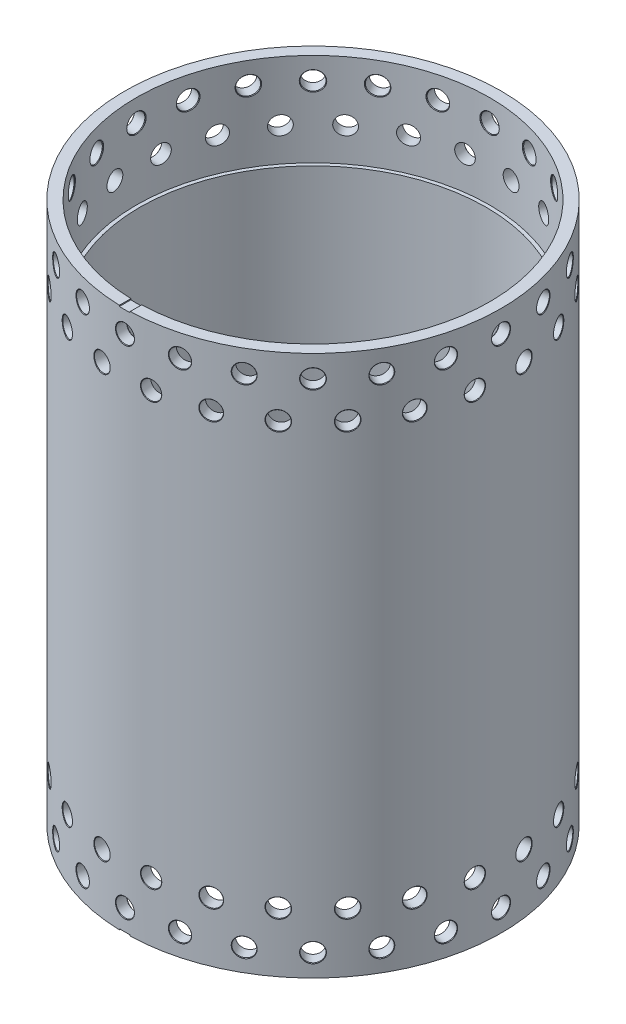
SolidWorks part; units mm, degrees
material "AW-6082-T6 (PA4)"
ref_plane "Płaszczyzna przednia" through (0, 0, 0) normal (0, 0, 1) x (1, 0, 0)
ref_plane "Płaszczyzna górna" through (0, 0, 0) normal (0, 1, 0) x (1, 0, 0)
ref_plane "Płaszczyzna prawa" through (0, 0, 0) normal (1, 0, 0) x (0, 0, -1)
sketch "Szkic1" plane through (0, 0, 0) normal (0, 1, 0) x (1, 0, 0)
  circle A0 centre (0, 0) radius 90
  circle A1 centre (0, 0) radius 80
  dimension "D1" = 10
  dimension "D2" = 180
  dimension "D3" = 160
extrude "Dodanie-wyciągnięcie1" add sketch "Szkic1" along normal blind 250
sketch "Szkic2" plane through (0, 250, 0) normal (0, 1, 0) x (1, 0, 0)
  circle A0 centre (0, 0) radius 87
  circle A1 centre (0, 0) radius 90 construction
  circle A2 centre (0, 0) radius 90
  dimension "D1" = 174
extrude "Wytnij-wyciągnięcie1" cut sketch "Szkic2" against normal through all
sketch "Szkic3" plane through (0, 250, 0) normal (0, 1, 0) x (1, 0, 0)
  circle A0 centre (0, 0) radius 81.7
  circle A1 centre (0, 0) radius 80 construction
  circle A2 centre (0, 0) radius 80
  dimension "D1" = 163.4
extrude "Wytnij-wyciągnięcie2" cut sketch "Szkic3" against normal blind 43
ref_plane "Płaszczyzna1" through (0, 0, 87) normal (0, 0, 1) x (1, 0, 0)
ref_plane "Płaszczyzna2" through (11.3558, 0, 86.2557) normal (0.1305, 0, 0.9914) x (0, 1, 0)
hole_wizard "Otwór Ø8.5 (8.5)1" positions "Szkic5" profile "Szkic6" hole size "Ø8.5" standard "DIN" end condition up to next
sketch "Szkic5" plane through (0, 0, 87) normal (0, 0, 1) x (1, 0, 0)
  line L0 (87, 250) -> (-87, 250) construction
  line L1 (87, 0) -> (87, 250) construction
  line L2 (-87, 250) -> (-87, 0) construction
  line L3 (87, 0) -> (87, 250)
  line L4 (-87, 250) -> (-87, 0)
  line L5 (0, 869.2816) -> (0, 760.9563) construction
  point P0 (0, 239.8)
  dimension "D1" = 10.2
sketch "Szkic6" plane through (0, 239.8, 87) normal (1, 0, 0) x (0, -1, 0)
  line L0 (0, 0) -> (0, 5.3)
  line L1 (0, 5.3) -> (4.5, 5.3)
  line L2 (4.25, 5.05) -> (4.25, 0.25)
  line L3 (4.25, 0.25) -> (4.5, 0)
  line L5 (4.5, 0) -> (0, 0)
  line L6 (-4.25, 0.25) -> (-4.5, 0) construction
  line L7 (4.5, 5.3) -> (4.25, 5.05)
  line L8 (-4.5, 5.3) -> (-4.25, 5.05) construction
  line L11 (0, -6.35) -> (0, 107.95) construction
  dimension "Średnica otworu na wylot" = 8.5
  dimension "Głębokość otworu na wylot" = 5.3
  dimension "Średnica zewnętrznego pogłębienia stożkowego" = 9
  dimension "Kąt zewnętrznego pogłębienia stożkowego" = 90
  dimension "Średnica wewnętrznego pogłębienia stożkowego" = 9
  dimension "Kąt wewnętrznego pogłębienia stożkowego" = 90
hole_wizard "Otwór Ø8.5 (8.5)2" positions "Szkic7" profile "Szkic8" hole size "Ø8.5" standard "BSI" end condition up to next
sketch "Szkic7" plane through (11.3558, 0, 86.2557) normal (0.1305, 0, 0.9914) x (0, 1, 0)
  line L0 (250, -87) -> (250, 87) construction
  line L1 (0, -87) -> (250, -87) construction
  line L2 (250, 87) -> (0, 87) construction
  line L3 (0, -87) -> (250, -87)
  line L4 (250, 87) -> (0, 87)
  line L5 (862.9512, 0) -> (744.0524, 0) construction
  ellipse E0 centre (239.8, 11.3231) end of major axis (244.05, 11.3231) minor radius 4.2136 construction
  point P0 (222.5, 0)
  dimension "D1" = 27.5
  dimension "D2" = 20.6762
sketch "Szkic8" plane through (11.3558, 222.5, 86.2557) normal (0, 1, 0) x (0.9914, 0, -0.1305)
  line L0 (0, 0) -> (0, 5.3)
  line L1 (0, 5.3) -> (4.25, 5.3)
  line L2 (4.25, 5.3) -> (4.25, 0.25)
  line L3 (4.25, 0.25) -> (4.5, 0)
  line L5 (4.5, 0) -> (0, 0)
  line L6 (-4.25, 0.25) -> (-4.5, 0) construction
  line L11 (0, -6.35) -> (0, 107.95) construction
  dimension "Średnica otworu na wylot" = 8.5
  dimension "Głębokość otworu na wylot" = 5.3
  dimension "Średnica zewnętrznego pogłębienia stożkowego" = 9
  dimension "Kąt zewnętrznego pogłębienia stożkowego" = 90
sketch "Szkic9" plane through (0, 250, 0) normal (0, 1, 0) x (1, 0, 0)
  line L0 (0, -87) -> (0, -1.7049) construction
  line L1 (2.5, -86.9641) -> (2.5, -79.9609)
  line L2 (-2.5, -86.9641) -> (-2.5, -79.9609)
  circle A0 centre (0, 0) radius 87 construction
  circle A1 centre (0, 0) radius 80 construction
  circle A2 centre (0, 0) radius 87
  circle A3 centre (0, 0) radius 80
  circle M6 centre (0, 0) radius 81.7
  circle M7 centre (0, 0) radius 87
  dimension "D1" = 5
extrude "Wytnij-wyciągnięcie3" cut sketch "Szkic9" against normal blind 0.5 contours L0 A2 L1 M6 | L0 L2 M7 M6 region at (-1.2501, 250, 84.3376) region at (1.2501, 250, 84.3376)
pattern_circular "Szyk kołowy1" count 24 over 360 about axis through (0, 0, 0) along (0, 1, 0) of "Otwór Ø8.5 (8.5)1", "Otwór Ø8.5 (8.5)2" reverse direction yes
ref_plane "Płaszczyzna3" through (0, 125, 0) normal (0, 1, 0) x (1, 0, 0)
mirror "Lustro1" about plane through (0, 125, 0) normal (0, 1, 0) of "Wytnij-wyciągnięcie3", "Wytnij-wyciągnięcie2", "Szyk kołowy1", "Otwór Ø8.5 (8.5)1", "Otwór Ø8.5 (8.5)2"
